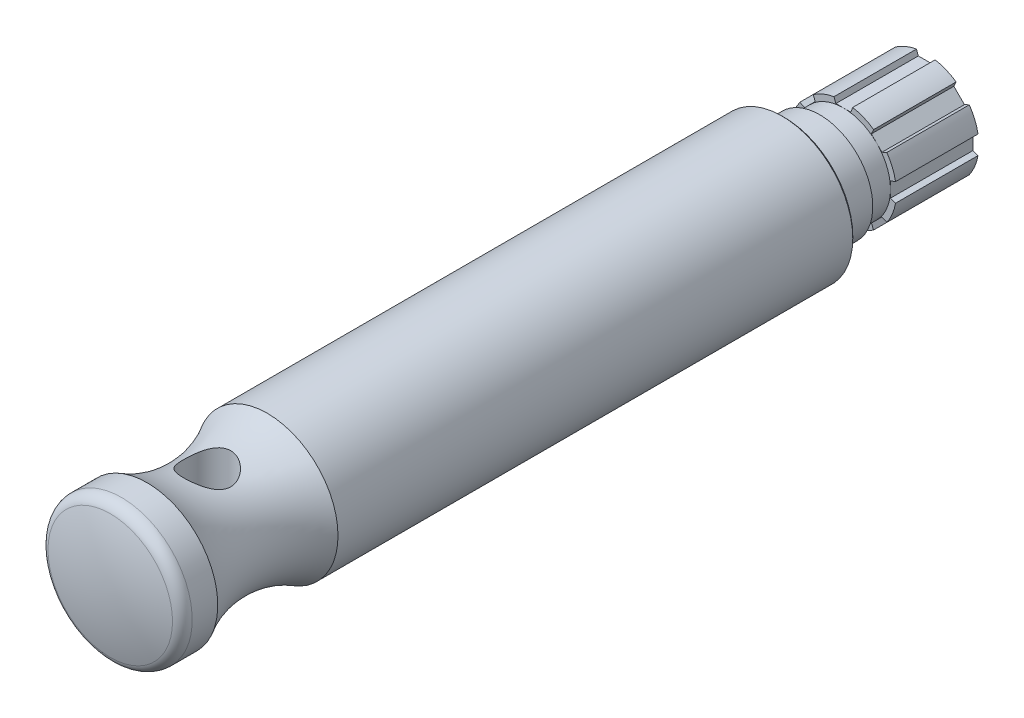
SolidWorks part; units mm, degrees
ref_plane "Front Plane" through (0, 0, 0) normal (0, 0, 1) x (1, 0, 0)
ref_plane "Top Plane" through (0, 0, 0) normal (0, 1, 0) x (1, 0, 0)
ref_plane "Right Plane" through (0, 0, 0) normal (1, 0, 0) x (0, 0, -1)
sketch "Sketch1" plane through (0, 0, 0) normal (0, 0, 1) x (1, 0, 0)
  circle A0 centre (0, 0) radius 3
  dimension "D1" = 6
extrude "Boss-Extrude1" add sketch "Sketch1" against normal blind 34.5
ref_axis "Axis1" through (0, 0, -34.5) along (0, 0, 1)
sketch "Sketch2" plane through (0, 0, 0) normal (1, 0, 0) x (0, 0, -1)
  line L0 (0, 2.3) -> (6.0068, 2.3) construction
  line L1 (0, 3) -> (0, -3) construction
  line L2 (34.5, 0) -> (0, 0) construction
  line L3 (30, 2.25) -> (30, 2)
  line L4 (34.5, 3) -> (28.5, 3)
  line L5 (34.5, 3) -> (34.5, 2.25)
  line L6 (34.5, 2.25) -> (31, 2.25)
  line L7 (28.5, 3) -> (28.5, 2.25)
  line L8 (30, 2) -> (31, 2)
  line L9 (31, 2) -> (31, 2.25)
  line L10 (34.5, -3) -> (34.5, 3) construction
  line L11 (30, 2.25) -> (28.5, 2.25)
  circle A0 centre (4, 7.3) radius 5
  dimension "D3" = 10
  dimension "D1" = 2.3
  dimension "D2" = 4
  dimension "D4" = 6
  dimension "D5" = 2.25
  dimension "D6" = 2
  dimension "D7" = 3.5
  dimension "D8" = 1
revolve "Cut-Revolve1" cut sketch "Sketch2" angle 360 about axis through (0, 0, -34.5) along (0, 0, 1)
sketch "Sketch3" plane through (0, 0, 0) normal (0, 1, 0) x (1, 0, 0)
  line L0 (0, 34.5) -> (0, 0) construction
  line L1 (-3, 0) -> (3, 0) construction
  circle A0 centre (0, 4) radius 1
  dimension "D1" = 4
  dimension "D2" = 2
extrude "Cut-Extrude1" cut sketch "Sketch3" against normal mid plane 6
dome "Dome1" faces to dome 1 distance 0.5 reverse direction no elliptical dome no face at (3, 0, 0) parameters "D1"=0.5
sketch "Sketch4" plane through (0, 0, -34.5) normal (0, 0, -1) x (-1, 0, 0)
  line L0 (-0.5, 2.5) -> (-0.318, 2)
  line L1 (-0.5, 2.5) -> (0.5, 2.5)
  line L2 (-0.5, 2.5) -> (-0.5, 2) construction
  line L3 (-0.5, 2) -> (0.5, 2) construction
  line L4 (0.5, 2.5) -> (0.5, 2) construction
  line L5 (-0.5, 2.5) -> (0.5, 2) construction
  line L6 (-0.5, 2) -> (0.5, 2.5) construction
  line L7 (-0.318, 2) -> (0.318, 2)
  line L8 (0.318, 2) -> (0.5, 2.5)
  line L9 (0, 2.25) -> (0, 2) construction
  circle A0 centre (0, 0) radius 2.25 construction
  circle A1 centre (0, 0) radius 2.25 construction
  point P0 (0, 2.25)
  dimension "D1" = 0.5
  dimension "D2" = 1
  dimension "D3" = 40
  dimension "D4" = 20
extrude "Cut-Extrude2" cut sketch "Sketch4" against normal blind 3.5
pattern_circular "CirPattern1" count 8 over 360 about axis through (0, 0, -34.5) along (0, 0, 1) of "Cut-Extrude2"
fillet "Fillet1" radius 0.5 1 edges at (3, 0, 0)
chamfer "Chamfer1" distance 0.1 angle 45 1 edges at (-3, 0, -28.5)
sketch "Sketch5" plane through (0, 0, -34.5) normal (0, 0, -1) x (-1, 0, 0)
  point P0 (0, 0)
hole_wizard "M3x0.5 Tapped Hole1" positions "3DSketch1" profile "Sketch6" tap size "M3x0.5" standard "ANSI Metric"
sketch3d "3DSketch1"
  point P0 (0, 0, -34.5)
sketch "Sketch6" plane through (0, 0, -34.5) normal (1, 0, 0) x (0, 1, 0)
  line L0 (0, 0) -> (0, 6.7511)
  line L1 (0, 6.7511) -> (1.25, 6)
  line L2 (1.25, 6) -> (1.25, 0)
  line L5 (1.25, 0) -> (0, 0)
  line L10 (0, 6.7511) -> (-1.25, 6) construction
  line L11 (0, -6.35) -> (0, 107.95) construction
  dimension "Tap Drill Dia." = 2.5
  dimension "Tap Drill Depth" = 6
  dimension "Drill Angle" = 118
cosmetic thread "Hole Thread1" parameters "D1"=5, "D2"=3
